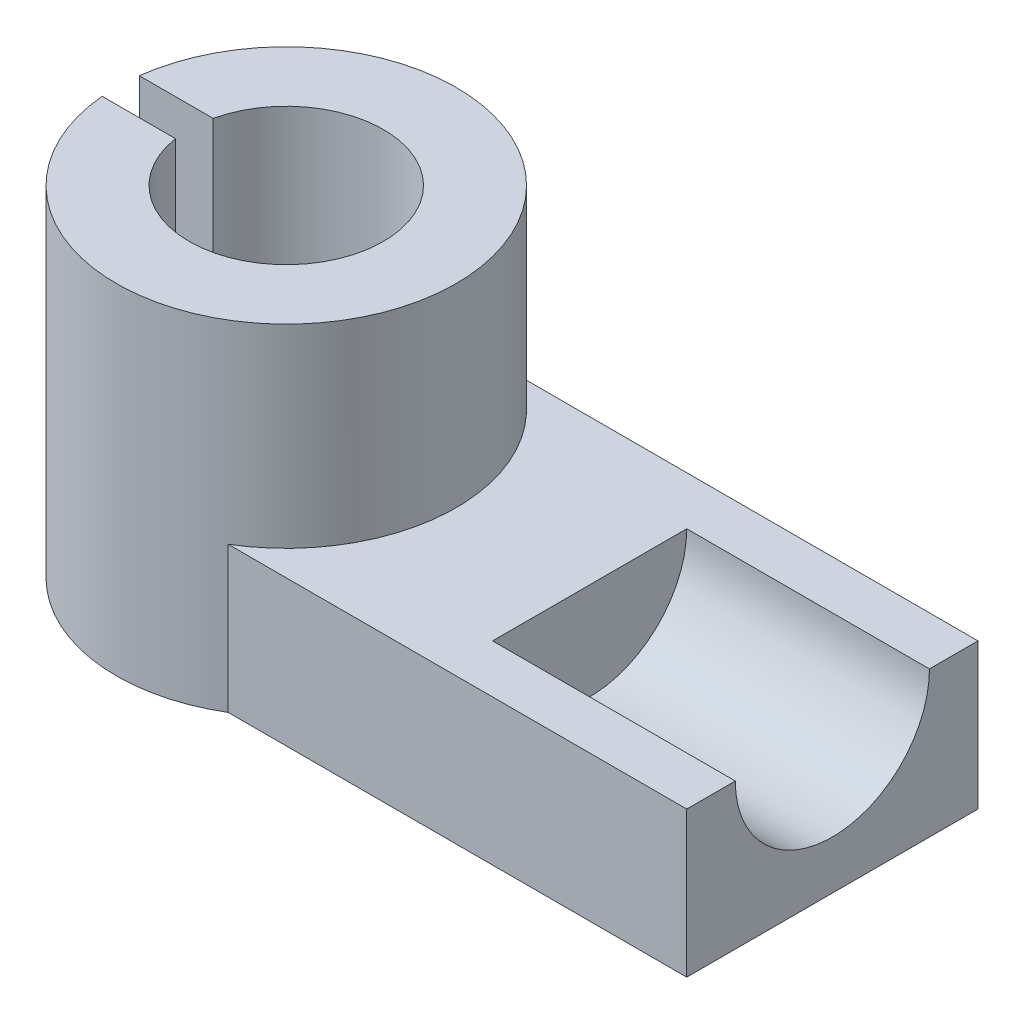
SolidWorks part; units mm, degrees
ref_plane "Front Plane" through (0, 0, 0) normal (0, 0, 1) x (1, 0, 0)
ref_plane "Top Plane" through (0, 0, 0) normal (0, 1, 0) x (1, 0, 0)
ref_plane "Right Plane" through (0, 0, 0) normal (1, 0, 0) x (0, 0, -1)
sketch "Sketch1" plane through (0, 0, 0) normal (0, 1, 0) x (1, 0, 0)
  line L0 (-44.3931, 24) -> (36.0098, 24) construction
  line L1 (14.4222, 0) -> (90, 0)
  line L3 (14.4222, 48) -> (90, 48)
  line L4 (90, 0) -> (90, 48)
  line L6 (0, 0) -> (0, -4) construction
  circle A0 centre (0, 24) radius 28
  circle A1 centre (0, 24) radius 16
  dimension "D3" = 56
  dimension "D4" = 32
  dimension "D1" = 90
  dimension "D2" = 48
extrude "Boss-Extrude1" add sketch "Sketch1" along normal blind 24 contours A0 L1 L4 L3 region at (56.9042, 0, -24)
extrude "Boss-Extrude2" add sketch "Sketch1<4>" along normal blind 56 contours A0 A1 region at (-27.208, 0, -24)
sketch "Sketch1<4>" plane through (0, 0, 0) normal (0, 1, 0) x (1, 0, 0) same geometry as "Sketch1"
sketch "Sketch2" plane through (0, 56, 0) normal (0, 1, 0) x (1, 0, 0)
  line L5 (-40.6619, 27.5522) -> (-2.051, 27.5522)
  line L6 (-40.6619, 27.5522) -> (-40.6619, 21.5522)
  line L11 (-40.6619, 21.5522) -> (-2.051, 21.5522)
  line L12 (-2.051, 27.5522) -> (-2.051, 21.5522)
  line L13 (-40.6619, 27.5522) -> (-2.051, 21.5522) construction
  line L14 (-40.6619, 21.5522) -> (-2.051, 27.5522) construction
  point P0 (-21.3565, 24.5522)
  dimension "D1" = 6
extrude "Cut-Extrude1" cut sketch "Sketch2" against normal through all
sketch "Sketch3" plane through (90, 0, 0) normal (1, 0, 0) x (0, 0, -1)
  line L0 (0, 24) -> (48, 24) construction
  circle A0 centre (24, 24) radius 16
  dimension "D1" = 32
extrude "Cut-Extrude2" cut sketch "Sketch3" against normal blind 40
